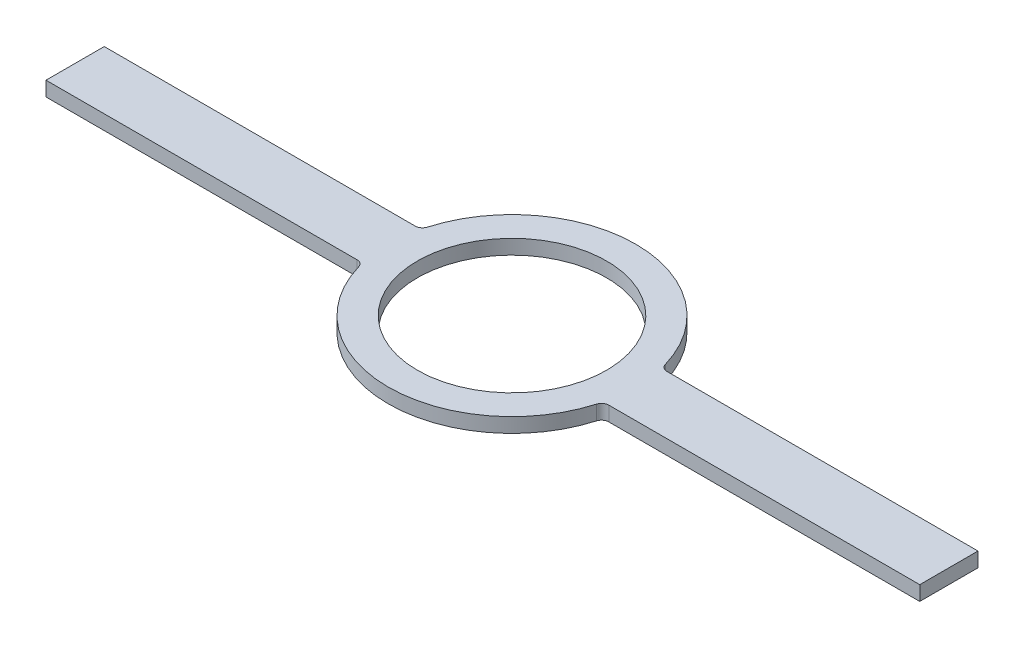
SolidWorks part; units mm, degrees
material "6061-T6 (SS)"
ref_plane "Front Plane" through (0, 0, 0) normal (0, 0, 1) x (1, 0, 0)
ref_plane "Top Plane" through (0, 0, 0) normal (0, 1, 0) x (1, 0, 0)
ref_plane "Right Plane" through (0, 0, 0) normal (1, 0, 0) x (0, 0, -1)
sketch "Sketch1" plane through (0, 0, 0) normal (0, 1, 0) x (1, 0, 0)
  line L0 (52.4596, 12.7) -> (190.5, 12.7)
  line L1 (-190.5, 12.7) -> (-52.4596, 12.7)
  line L2 (-190.5, 12.7) -> (-190.5, -12.7)
  line L3 (-190.5, -12.7) -> (-52.4596, -12.7)
  line L4 (190.5, 12.7) -> (190.5, -12.7)
  line L5 (-190.5, 12.7) -> (190.5, -12.7) construction
  line L6 (-190.5, -12.7) -> (190.5, 12.7) construction
  line L7 (52.4596, -12.7) -> (190.5, -12.7)
  circle A0 centre (0, 0) radius 41.275
  arc A1 (-52.4596, -12.7) -> (52.4596, -12.7) centre (0, 0) ccw
  arc A2 (52.4596, 12.7) -> (-52.4596, 12.7) centre (0, 0) ccw
  point P0 (0, 0)
  dimension "D3" = 82.55
  dimension "D4" = 12.7
  dimension "D1" = 381
  dimension "D2" = 25.4
extrude "Boss-Extrude1" add sketch "Sketch1" along normal blind 6.35
fillet "Fillet1" radius 3.175 4 edges at (-52.4596, 3.175, -12.7) (52.4596, 3.175, -12.7) (52.4596, 3.175, 12.7) (-52.4596, 3.175, 12.7)
